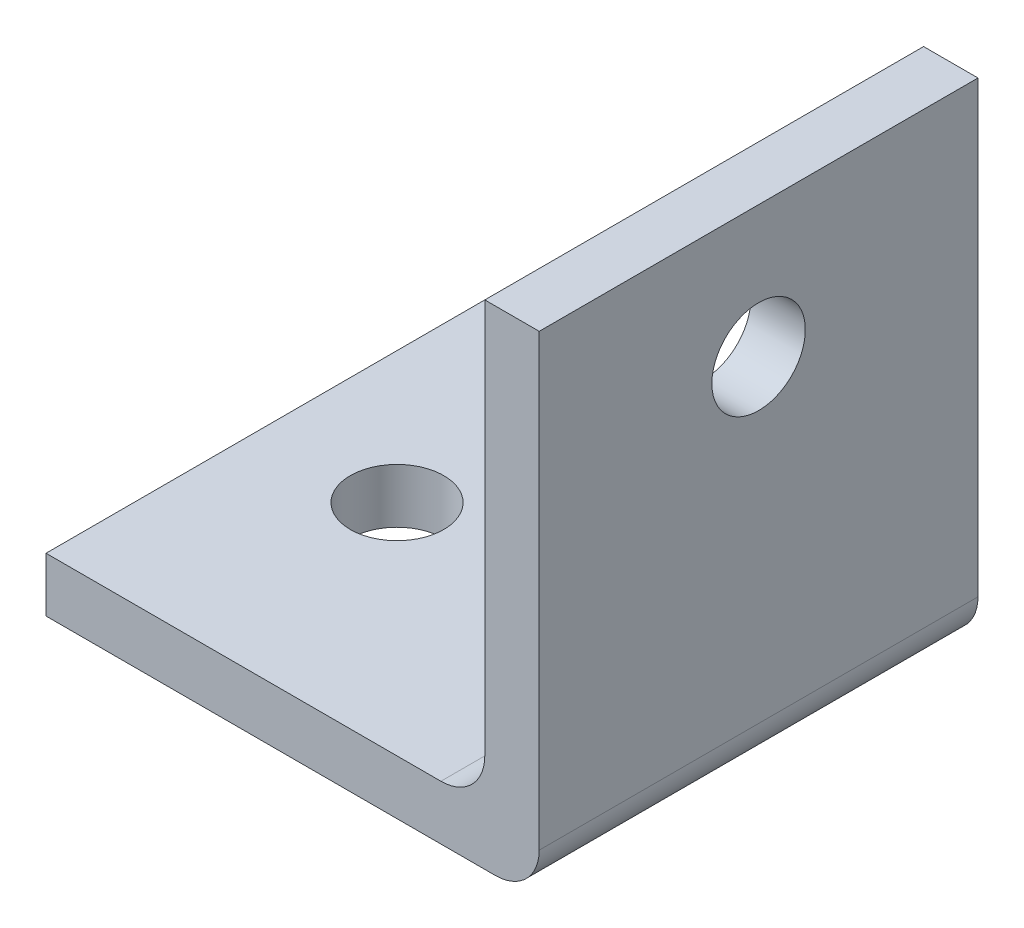
SolidWorks part; units mm, degrees
ref_plane "Front Plane" through (0, 0, 0) normal (0, 0, 1) x (1, 0, 0)
ref_plane "Top Plane" through (0, 0, 0) normal (0, 1, 0) x (1, 0, 0)
ref_plane "Right Plane" through (0, 0, 0) normal (1, 0, 0) x (0, 0, -1)
sketch "Sketch1" plane through (0, 0, 0) normal (0, 0, 1) x (1, 0, 0)
  line L0 (0, 0) -> (14.2748, 0)
  line L2 (0, 0) -> (0, 1.5748)
  line L3 (0, 1.5748) -> (12.7, 1.5748)
  line L6 (12.7, 1.5748) -> (12.7, 14.2748)
  line L7 (12.7, 14.2748) -> (14.2748, 14.2748)
  line L8 (14.2748, 0) -> (14.2748, 14.2748)
  dimension "D1" = 1.5748
  dimension "D2" = 14.2748
extrude "Boss-Extrude1" add sketch "Sketch1" along normal blind 12.7
fillet "Fillet1" radius 1.27 2 edges at (12.7, 1.5748, 6.35) (14.2748, 0, 6.35)
sketch "Sketch4" plane through (12.7, 0, 0) normal (-1, 0, 0) x (0, 0, 1)
  line L0 (12.7, 14.2748) -> (0, 14.2748) construction
  line L1 (12.7, 0) -> (0, 0) construction
  point P0 (6.35, 14.2748)
  point P1 (6.35, 10.4648)
  dimension "D1" = 10.4648
sketch "Sketch5" plane through (0, 1.5748, 0) normal (0, 1, 0) x (1, 0, 0)
  line L0 (14.2748, -12.7) -> (14.2748, 0) construction
  point P0 (3.81, -6.35)
  dimension "D1" = 10.4648
hole_wizard "#6-32 Tapped Hole1" positions "Sketch7" profile "Sketch6" tap size "#6-32" standard "ANSI Inch" end condition through all
sketch "Sketch7" plane through (12.7, 0, 0) normal (-1, 0, 0) x (0, 0, 1)
  point P0 (6.35, 10.4648)
sketch "Sketch6" plane through (12.7, 10.4648, 6.35) normal (0, 1, 0) x (0, 0, 1)
  line L0 (0, 0) -> (0, 1.5748)
  line L1 (0, 1.5748) -> (1.3525, 1.5748)
  line L2 (1.3525, 1.5748) -> (1.3525, 0)
  line L5 (1.3525, 0) -> (0, 0)
  line L11 (0, -6.35) -> (0, 107.95) construction
  dimension "Thru Tap Drill Dia." = 2.7051
  dimension "Thru Tap Drill Depth" = 1.5748
cosmetic thread "Hole Thread1"
hole_wizard "#6-32 Tapped Hole2" positions "Sketch9" profile "Sketch8" tap size "#6-32" standard "ANSI Inch" end condition through all
sketch "Sketch9" plane through (0, 1.5748, 0) normal (0, 1, 0) x (1, 0, 0)
  point P0 (3.81, -6.35)
sketch "Sketch8" plane through (3.81, 1.5748, 6.35) normal (1, 0, 0) x (0, 0, 1)
  line L0 (0, 0) -> (0, 1.5748)
  line L1 (0, 1.5748) -> (1.3525, 1.5748)
  line L2 (1.3525, 1.5748) -> (1.3525, 0)
  line L5 (1.3525, 0) -> (0, 0)
  line L11 (0, -6.35) -> (0, 107.95) construction
  dimension "Thru Tap Drill Dia." = 2.7051
  dimension "Thru Tap Drill Depth" = 1.5748
cosmetic thread "Hole Thread2"
